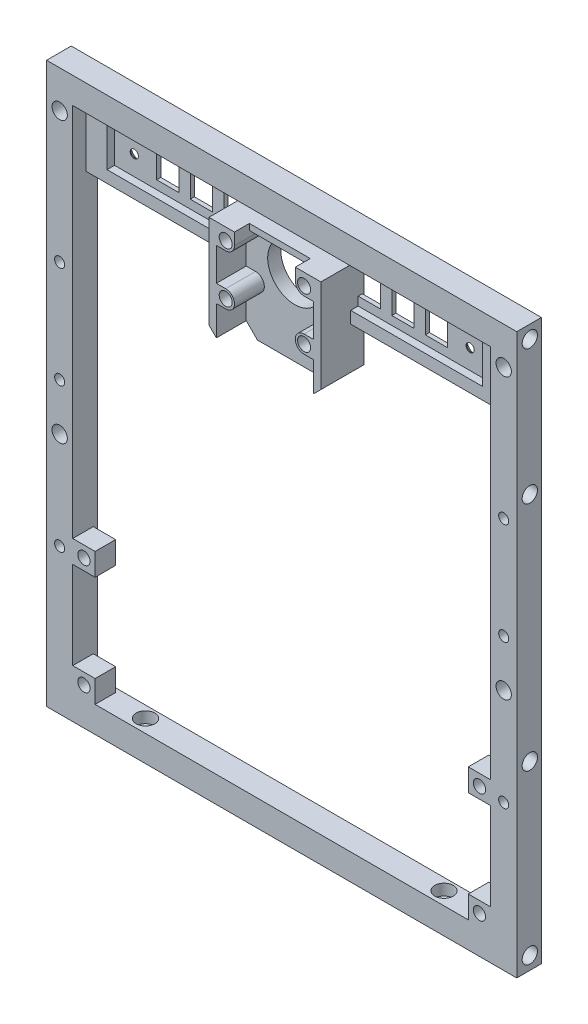
SolidWorks part; units mm, degrees
ref_plane "Front Plane" through (0, 0, 0) normal (0, 0, 1) x (1, 0, 0)
ref_plane "Top Plane" through (0, 0, 0) normal (0, 1, 0) x (1, 0, 0)
ref_plane "Right Plane" through (0, 0, 0) normal (1, 0, 0) x (0, 0, -1)
sketch "Sketch1" plane through (0, 0, 0) normal (0, 0, 1) x (1, 0, 0)
  line L1 (-63, -75) -> (63, -75)
  line L2 (-63, -75) -> (-63, 75)
  line L3 (-63, 75) -> (63, 75)
  line L4 (63, -75) -> (63, 75)
  line L5 (-63, -75) -> (63, 75) construction
  line L6 (-63, 75) -> (63, -75) construction
  line L7 (-56, -68) -> (56, -68)
  line L8 (-56, -68) -> (-56, 68)
  line L9 (-56, 68) -> (56, 68)
  line L10 (56, -68) -> (56, 68)
  line L11 (-56, -68) -> (56, 68) construction
  line L12 (-56, 68) -> (56, -68) construction
  point P0 (0, 0)
  point P6 (0, 0)
  dimension "D1" = 126
  dimension "D2" = 150
  dimension "D3" = 7
  dimension "D4" = 7
extrude "Boss-Extrude1" add sketch "Sketch1" along normal blind 7
sketch "Sketch2" plane through (-63, 0, 0) normal (-1, 0, 0) x (0, 0, 1)
  line L0 (3.5, 71.5) -> (3.5, -71.5) construction
  line L1 (7, 75) -> (0, 75) construction
  circle A0 centre (3.5, -71.5) radius 2.05
  circle A2 centre (3.5, 71.5) radius 2.05
  circle A3 centre (3.5, 35.5) radius 2.05
  circle A4 centre (3.5, -26.5) radius 2.05
  point P2 (3.5, 0)
  point P7 (3.5, 75)
  dimension "D2" = 4.1
  dimension "D3" = 36
  dimension "D4" = 45
  dimension "D1" = 3.5
extrude "Cut-Extrude1" cut sketch "Sketch2" against normal blind 6
mirror "Mirror1" about plane through (0, 0, 0) normal (1, 0, 0) of "Cut-Extrude1"
sketch "Sketch3" plane through (0, -68, 0) normal (0, 1, 0) x (1, 0, 0)
  line L0 (0, 0) -> (0, -7) construction
  line L1 (-56, 0) -> (56, 0) construction
  line L2 (-56, -7) -> (56, -7) construction
  line L3 (40, -3.5) -> (-40, -3.5) construction
  circle A0 centre (40, -3.5) radius 1.35
  circle A1 centre (-40, -3.5) radius 1.35
  point P9 (0, -3.5)
  dimension "D1" = 2.7
  dimension "D2" = 80
extrude "Cut-Extrude2" cut sketch "Sketch3" against normal through all
sketch "Sketch4" plane through (0, -68, 0) normal (0, 1, 0) x (1, 0, 0)
  circle A0 centre (40, -3.5) radius 2.5
  circle A1 centre (-40, -3.5) radius 2.5
  dimension "D1" = 5
extrude "Cut-Extrude3" cut sketch "Sketch4" against normal blind 3
sketch "Sketch5" plane through (0, 0, 0) normal (0, 0, -1) x (-1, 0, 0)
  line L0 (-59.5, -75) -> (-59.5, 75) construction
  line L1 (63, -75) -> (-63, -75) construction
  line L2 (-63, 75) -> (63, 75) construction
  line L3 (-56, 0) -> (-63, 0) construction
  line L4 (-56, -68) -> (-56, 68) construction
  line L5 (-63, -75) -> (-63, 75) construction
  line L6 (0, 75) -> (0, -75) construction
  line L7 (56, -68) -> (-56, -68) construction
  circle A0 centre (-59.5, 2.6) radius 1.35
  circle A1 centre (59.5, 2.6) radius 1.35
  circle A2 centre (-59.5, -36) radius 1.35
  circle A3 centre (59.5, -36) radius 1.35
  circle A4 centre (-59.5, 29.9) radius 1.35
  circle A5 centre (59.5, 29.9) radius 1.35
  point P12 (-59.5, 0)
  point P13 (-59.5, 0)
  dimension "D1" = 2.7
  dimension "D2" = 2.6
  dimension "D3" = 32
  dimension "D4" = 45.1
extrude "Cut-Extrude4" cut sketch "Sketch5" against normal through all
sketch "Sketch6" plane through (0, 0, 0) normal (0, 0, -1) x (-1, 0, 0)
  circle A0 centre (-59.5, 2.6) radius 2.5
  circle A1 centre (59.5, 2.6) radius 2.5
  circle A2 centre (-59.5, -36) radius 2.5
  circle A3 centre (59.5, -36) radius 2.5
  circle A4 centre (-59.5, 29.9) radius 2.5
  circle A5 centre (59.5, 29.9) radius 2.5
  dimension "D1" = 5
extrude "Cut-Extrude5" cut sketch "Sketch6" against normal blind 3
sketch "Sketch7" plane through (0, 0, 0) normal (0, 0, -1) x (-1, 0, 0)
  line L0 (-56, 68) -> (-63, 68) construction
  line L1 (-63, -75) -> (-63, 75) construction
  line L2 (-59.5, 65) -> (-59.5, -10) construction
  line L3 (-63, 75) -> (63, 75) construction
  circle A0 centre (-59.5, 65) radius 2.05
  circle A1 centre (-59.5, -10) radius 2.05
  point P8 (-59.5, 68)
  dimension "D1" = 4.1
  dimension "D2" = 10
  dimension "D3" = 75
extrude "Cut-Extrude6" cut sketch "Sketch7" against normal through all
mirror "Mirror2" about plane through (0, 0, 0) normal (1, 0, 0) of "Cut-Extrude6"
sketch "Sketch8" plane through (0, 0, 3) normal (0, 0, -1) x (-1, 0, 0)
  line L0 (-60.85, 32.0042) -> (-60.85, 27.7958)
  line L2 (-60.85, 0.4958) -> (-60.85, 4.7042)
  line L4 (-58.15, 0.4958) -> (-58.15, 4.7042)
  line L5 (-60.85, 0.4958) -> (-58.15, 4.7042) construction
  line L6 (-60.85, 4.7042) -> (-58.15, 0.4958) construction
  line L8 (-60.85, -38.1042) -> (-60.85, -33.8958)
  line L10 (-58.15, -38.1042) -> (-58.15, -33.8958)
  line L11 (-60.85, -38.1042) -> (-58.15, -33.8958) construction
  line L12 (-60.85, -33.8958) -> (-58.15, -38.1042) construction
  line L13 (-58.15, 32.0042) -> (-58.15, 27.7958)
  circle A0 centre (-59.5, 2.6) radius 2.5 construction
  circle A1 centre (-59.5, -36) radius 2.5 construction
  circle A2 centre (-59.5, -36) radius 2.5 construction
  arc A3 (-58.15, 4.7042) -> (-60.85, 4.7042) centre (-59.5, 2.6) ccw
  arc A4 (-58.15, -33.8958) -> (-60.85, -33.8958) centre (-59.5, -36) ccw
  circle A5 centre (-59.5, 2.6) radius 1.35 construction
  circle A6 centre (-59.5, -36) radius 1.35 construction
  arc A7 (-60.85, -38.1042) -> (-58.15, -38.1042) centre (-59.5, -36) ccw
  arc A8 (-60.85, 0.4958) -> (-58.15, 0.4958) centre (-59.5, 2.6) ccw
  circle A9 centre (-59.5, 29.9) radius 2.5 construction
  arc A10 (-60.85, 32.0042) -> (-58.15, 32.0042) centre (-59.5, 29.9) cw
  arc A11 (-58.15, 27.7958) -> (-60.85, 27.7958) centre (-59.5, 29.9) cw
  point P0 (-59.5, 2.6)
  point P8 (-59.5, -36)
extrude "Cut-Extrude7" cut sketch "Sketch8" against normal blind 0.2
sketch "Sketch9" plane through (0, 0, 3.2) normal (0, 0, -1) x (-1, 0, 0)
  line L0 (-58.15, 2.6) -> (-58.15, 4.7042) construction
  line L1 (-60.85, 1.25) -> (-58.15, 1.25)
  line L2 (-60.85, 1.25) -> (-60.85, 3.95)
  line L3 (-60.85, 3.95) -> (-58.15, 3.95)
  line L4 (-58.15, 1.25) -> (-58.15, 3.95)
  line L5 (-60.85, 1.25) -> (-58.15, 3.95) construction
  line L6 (-60.85, 3.95) -> (-58.15, 1.25) construction
  line L7 (-58.15, -38.1042) -> (-58.15, -33.8958) construction
  line L8 (-60.85, -37.35) -> (-58.15, -37.35)
  line L9 (-60.85, -37.35) -> (-60.85, -34.65)
  line L10 (-60.85, -34.65) -> (-58.15, -34.65)
  line L11 (-58.15, -37.35) -> (-58.15, -34.65)
  line L12 (-60.85, -37.35) -> (-58.15, -34.65) construction
  line L13 (-60.85, -34.65) -> (-58.15, -37.35) construction
  arc A0 (-58.15, 2.6) -> (-60.85, 2.6) centre (-59.5, 2.6) ccw construction
  point P0 (-59.5, 2.6)
  point P8 (-59.5, -36)
extrude "Cut-Extrude8" cut sketch "Sketch9" against normal blind 0.2
mirror "Mirror3" about plane through (0, 0, 0) normal (1, 0, 0) of "Cut-Extrude8", "Cut-Extrude7"
sketch "Sketch10" plane through (0, 0, 7) normal (0, 0, 1) x (1, 0, 0)
  line L0 (56, -68) -> (56, 68) construction
  line L1 (56, -68) -> (50, -68)
  line L2 (56, -68) -> (56, -62)
  line L3 (56, -62) -> (50, -62)
  line L4 (50, -68) -> (50, -62)
  line L5 (56, -38.5) -> (50, -38.5)
  line L6 (56, -38.5) -> (56, -32.5)
  line L7 (56, -32.5) -> (50, -32.5)
  line L8 (50, -38.5) -> (50, -32.5)
  line L9 (-56, -68) -> (56, -68) construction
  dimension "D1" = 6
  dimension "D2" = 35.5
extrude "Boss-Extrude2" add sketch "Sketch10" against normal offset from surface (5.5 mm away) 1.5 up to face at (-57.45, -10, 0)
sketch "Sketch11" plane through (0, 0, 1.5) normal (0, 0, -1) x (-1, 0, 0)
  line L0 (-56, -38.5) -> (-50, -32.5) construction
  line L2 (-56, -68) -> (-50, -62) construction
  circle A0 centre (-53, -35.5) radius 1.65
  circle A1 centre (-53, -65) radius 1.65
  dimension "D1" = 3.3
extrude "Cut-Extrude9" cut sketch "Sketch11" against normal through all
mirror "Mirror4" about plane through (0, 0, 0) normal (1, 0, 0) of "Cut-Extrude9", "Boss-Extrude2"
sketch "Sketch12" plane through (0, 0, 0) normal (0, 0, -1) x (-1, 0, 0)
  line L0 (56, 68) -> (56, -68) construction
  line L1 (-56, 68) -> (56, 68)
  line L2 (-56, 68) -> (-56, 51)
  line L3 (-56, 51) -> (56, 51)
  line L4 (56, 68) -> (56, 51)
  dimension "D1" = 17
extrude "Boss-Extrude3" add sketch "Sketch12" against normal blind 1.5
sketch "Sketch13" plane through (0, 0, 1.5) normal (0, 0, 1) x (1, 0, 0)
  line L0 (-56, 68) -> (56, 51) construction
  line L2 (-50.3, 54.2) -> (50.3, 54.2)
  line L3 (-50.3, 54.2) -> (-50.3, 64.8)
  line L4 (-50.3, 64.8) -> (50.3, 64.8)
  line L5 (50.3, 54.2) -> (50.3, 64.8)
  line L6 (-50.3, 54.2) -> (50.3, 64.8) construction
  line L7 (-50.3, 64.8) -> (50.3, 54.2) construction
  line L8 (-56, 51) -> (56, 51)
  line L9 (-56, 51) -> (-56, 68)
  line L10 (-56, 68) -> (56, 68)
  line L11 (56, 51) -> (56, 68)
  line L12 (-56, 51) -> (56, 68) construction
  line L13 (-56, 68) -> (56, 51) construction
  point P4 (0, 59.5)
  point P9 (0, 59.5)
  dimension "D1" = 100.6
  dimension "D2" = 10.6
extrude "Boss-Extrude4" add sketch "Sketch13" along normal blind 2
sketch "Sketch14" plane through (0, 0, 1.5) normal (0, 0, 1) x (1, 0, 0)
  line L0 (0, 64.8) -> (0, 54.2) construction
  line L1 (50.3, 64.8) -> (-50.3, 64.8) construction
  line L2 (-50.3, 54.2) -> (50.3, 54.2) construction
  line L3 (-50.3, 59.5) -> (50.3, 59.5) construction
  line L4 (50.3, 54.2) -> (50.3, 64.8) construction
  line L5 (-33, 62.5) -> (-39, 62.5)
  line L6 (-3.25, 57.5) -> (3.25, 57.5)
  line L7 (-3.25, 57.5) -> (-3.25, 61.5)
  line L8 (-3.25, 61.5) -> (3.25, 61.5)
  line L9 (3.25, 57.5) -> (3.25, 61.5)
  line L10 (-3.25, 57.5) -> (3.25, 61.5) construction
  line L11 (-3.25, 61.5) -> (3.25, 57.5) construction
  line L12 (6, 56.5) -> (12, 56.5)
  line L13 (6, 56.5) -> (6, 62.5)
  line L14 (6, 62.5) -> (12, 62.5)
  line L15 (12, 56.5) -> (12, 62.5)
  line L16 (6, 56.5) -> (12, 62.5) construction
  line L17 (6, 62.5) -> (12, 56.5) construction
  line L18 (15, 56.5) -> (21, 56.5)
  line L19 (15, 56.5) -> (15, 62.5)
  line L20 (15, 62.5) -> (21, 62.5)
  line L21 (21, 56.5) -> (21, 62.5)
  line L22 (15, 56.5) -> (21, 62.5) construction
  line L23 (15, 62.5) -> (21, 56.5) construction
  line L24 (24, 56.5) -> (30, 56.5)
  line L25 (24, 56.5) -> (24, 62.5)
  line L26 (24, 62.5) -> (30, 62.5)
  line L27 (30, 56.5) -> (30, 62.5)
  line L28 (24, 56.5) -> (30, 62.5) construction
  line L29 (24, 62.5) -> (30, 56.5) construction
  line L30 (33, 56.5) -> (39, 56.5)
  line L31 (33, 56.5) -> (33, 62.5)
  line L32 (33, 62.5) -> (39, 62.5)
  line L33 (39, 56.5) -> (39, 62.5)
  line L34 (33, 56.5) -> (39, 62.5) construction
  line L35 (33, 62.5) -> (39, 56.5) construction
  line L36 (-39, 56.5) -> (-39, 62.5)
  line L37 (-33, 56.5) -> (-39, 56.5)
  line L38 (-33, 56.5) -> (-33, 62.5)
  line L39 (-24, 62.5) -> (-30, 62.5)
  line L40 (-30, 56.5) -> (-30, 62.5)
  line L41 (-24, 56.5) -> (-30, 56.5)
  line L42 (-24, 56.5) -> (-24, 62.5)
  line L43 (-15, 62.5) -> (-21, 62.5)
  line L44 (-21, 56.5) -> (-21, 62.5)
  line L45 (-15, 56.5) -> (-21, 56.5)
  line L46 (-15, 56.5) -> (-15, 62.5)
  line L47 (-6, 62.5) -> (-12, 62.5)
  line L48 (-12, 56.5) -> (-12, 62.5)
  line L49 (-6, 56.5) -> (-12, 56.5)
  line L50 (-6, 56.5) -> (-6, 62.5)
  circle A0 centre (-45, 59.5) radius 1.3 construction
  circle A1 centre (45, 59.5) radius 1.3 construction
  point P6 (0, 59.5)
  point P11 (0, 59.5)
  point P16 (9, 59.5)
  point P21 (18, 59.5)
  point P26 (27, 59.5)
  point P31 (36, 59.5)
  dimension "D10" = 2.6
  dimension "D9" = 45
  dimension "D1" = 6.5
  dimension "D2" = 4
  dimension "D3" = 6
  dimension "D4" = 9
  dimension "D5" = 9
  dimension "D6" = 9
  dimension "D7" = 9
  dimension "D8" = 45
extrude "Cut-Extrude10" cut sketch "Sketch14" against normal through all
sketch "Sketch15" plane through (0, 0, 1.5) normal (0, 0, 1) x (1, 0, 0)
  circle A0 centre (-45, 59.5) radius 1
  circle A1 centre (45, 59.5) radius 1
  dimension "D1" = 2
extrude "Boss-Extrude5" add sketch "Sketch15" along normal up to surface (2 mm away) up to face at (0, 59.5, 3.5)
chamfer "Chamfer1" distance 0.4 angle 45 4 edges at (-56, -8.5, 0) (56, -8.5, 0) (0, -68, 0) (0, 51, 0)
chamfer "Chamfer2" distance 0.4 angle 45 4 edges at (0, 75, 0) (-63, 0, 0) (0, -75, 0) (63, 0, 0)
chamfer "Chamfer3" distance 0.4 angle 45 36 edges at (-36, 56.5, 0) (-39, 59.5, 0) (-36, 62.5, 0) (-33, 59.5, 0) (-27, 56.5, 0) (-30, 59.5, 0) (-27, 62.5, 0) (-24, 59.5, 0) (-18, 56.5, 0) (-21, 59.5, 0) (-18, 62.5, 0) (-15, 59.5, 0) (-9, 56.5, 0) (-12, 59.5, 0) (-9, 62.5, 0) (-6, 59.5, 0) (0, 57.5, 0) (-3.25, 59.5, 0) (0, 61.5, 0) (3.25, 59.5, 0) (9, 56.5, 0) (6, 59.5, 0) (9, 62.5, 0) (12, 59.5, 0) (18, 56.5, 0) (15, 59.5, 0) (18, 62.5, 0) (21, 59.5, 0) (36, 56.5, 0) (33, 59.5, 0) (36, 62.5, 0) (39, 59.5, 0) (27, 56.5, 0) (24, 59.5, 0) (27, 62.5, 0) (30, 59.5, 0)
sketch "Sketch16" plane through (0, 0, 7) normal (0, 0, 1) x (1, 0, 0)
  line L0 (-50, 51) -> (-50, 54.2)
  line L1 (-56, -32.5) -> (-50, -32.5)
  line L2 (-56, -32.5) -> (-56, -26.5)
  line L3 (-56, -26.5) -> (-50, -26.5)
  line L4 (-50, -32.5) -> (-50, -26.5)
  line L5 (56, -32.5) -> (50, -32.5)
  line L6 (56, -32.5) -> (56, -26.5)
  line L7 (56, -26.5) -> (50, -26.5)
  line L8 (50, -32.5) -> (50, -26.5)
  line L9 (56, 51) -> (50, 51) construction
  line L10 (56, 51) -> (56, 45)
  line L11 (56, 45) -> (50, 45)
  line L12 (50, 51) -> (50, 45)
  line L13 (-56, 51) -> (-50, 51) construction
  line L14 (-56, 51) -> (-56, 45)
  line L15 (-56, 45) -> (-50, 45)
  line L16 (-50, 51) -> (-50, 45)
  line L17 (-50.3, 54.2) -> (50.3, 54.2) construction
  line L18 (-50, 54.2) -> (-56, 54.2)
  line L19 (-56, 68) -> (-56, 51) construction
  line L20 (-56, 54.2) -> (-56, 51)
  line L21 (50, 51) -> (50, 54.2)
  line L22 (50, 54.2) -> (56, 54.2)
  line L23 (56, 51) -> (56, 68) construction
  line L24 (56, 54.2) -> (56, 51)
  dimension "D1" = 6
extrude "Boss-Extrude7" add sketch "Sketch16" against normal offset from surface (5.5 mm away) 1.5 up to face at (-36, 59.5, 0)
sketch "Sketch17" plane through (0, 0, 1.5) normal (0, 0, -1) x (-1, 0, 0)
  line L0 (-50, 45) -> (50, -26.5) construction
  line L1 (-50, -26.5) -> (-50, -38.5) construction
  line L2 (-53, -29.5) -> (53, -29.5) construction
  line L3 (-53, -29.5) -> (-53, 48) construction
  line L4 (-53, 48) -> (53, 48) construction
  line L5 (53, -29.5) -> (53, 48) construction
  line L6 (-53, -29.5) -> (53, 48) construction
  line L7 (-53, 48) -> (53, -29.5) construction
  line L8 (50, -26.5) -> (56, -26.5) construction
  circle A0 centre (-53, -29.5) radius 1.65
  circle A1 centre (53, -29.5) radius 1.65
  circle A2 centre (53, 48) radius 1.65
  circle A3 centre (-53, 48) radius 1.65
  point P4 (0, 9.25)
  dimension "D3" = 3.3
  dimension "D1" = 3
  dimension "D2" = 3
extrude "Cut-Extrude11" cut sketch "Sketch17" against normal through all
sketch "Sketch18" plane through (0, 0, 1.5) normal (0, 0, 1) x (1, 0, 0)
  circle A0 centre (-45, 59.5) radius 1.1
  circle A1 centre (45, 59.5) radius 1.1
  dimension "D1" = 2.2
extrude "Cut-Extrude12" cut sketch "Sketch18" against normal through all both and the other way through all
chamfer "Chamfer4" distance 1.3 angle 45 2 edges at (-43.9, 59.5, 0) (46.1, 59.5, 0)
sketch "Skizze1" plane through (0, 0, 7) normal (0, 0, 1) x (1, 0, 0)
  line L0 (-56, -38.5) -> (-56, -26.5) construction
  line L1 (56, 51) -> (-56, 51)
  line L2 (56, 51) -> (56, -32.5)
  line L3 (56, -32.5) -> (-56, -32.5)
  line L4 (-56, 51) -> (-56, -32.5)
extrude "Schnitt-Linear austragen1" cut sketch "Skizze1" against normal up to surface (5.5 mm away) up to face at (-54.65, 48, 1.5)
sketch "Skizze2" plane through (0, 0, 7) normal (0, 0, 1) x (1, 0, 0)
  line L1 (-56, 54.2) -> (56, 54.2)
  line L2 (-56, 54.2) -> (-56, 51)
  line L3 (-56, 51) -> (56, 51)
  line L4 (56, 54.2) -> (56, 51)
extrude "Schnitt-Linear austragen2" cut sketch "Skizze2" against normal up to surface (3.5 mm away) up to face at (0, 52.6, 3.5)
sketch "Skizze3" plane through (0, 0, 3.5) normal (0, 0, 1) x (1, 0, 0)
  line L0 (0, 51) -> (0, 14.1518) construction
  line L2 (50.3, 64.8) -> (-50.3, 64.8) construction
  line L3 (-15, 34.8) -> (15, 34.8)
  line L4 (-15, 34.8) -> (-15, 64.8)
  line L5 (-15, 64.8) -> (15, 64.8)
  line L6 (15, 34.8) -> (15, 64.8)
  line L7 (-15, 34.8) -> (15, 64.8) construction
  line L8 (-15, 64.8) -> (15, 34.8) construction
  line L10 (-12.5, 37.3) -> (12.5, 37.3)
  line L11 (-12.5, 37.3) -> (-12.5, 62.3)
  line L12 (-12.5, 62.3) -> (12.5, 62.3)
  line L13 (12.5, 37.3) -> (12.5, 62.3)
  line L14 (-12.5, 37.3) -> (12.5, 62.3) construction
  line L15 (-12.5, 62.3) -> (12.5, 37.3) construction
  point P1 (0, 49.8)
  point P9 (0, 49.8)
  point P16 (0, 45.1863)
  point P17 (-12.5, 37.3)
  line M7 (-56, 51) -> (56, 51)
  line M10 (50.3, 54.2) -> (-50.3, 54.2)
  line M12 (-50.3, 64.8) -> (50.3, 64.8)
  dimension "D1" = 30
  dimension "D2" = 25
extrude "Aufsatz-Linear austragen1" add sketch "Skizze3" against normal up to surface (3.5 mm away) contours L10 L13 L11 M7 | L13 L10 L11 L4 L3 L6 M7 | L13 L12 L11 M10 | L13 L6 L4 L11 L12 M10 M12 | L13 L6 M7 M10 | L13 L11 M7 M10 | L11 L4 M7 M10 region at (-14.6591, 42.9, 3.5) region at (-13.75, 52.6, 3.5) region at (13.75, 52.6, 3.5) region at (-14.6818, 59.5, 3.5) region at (0, 44.15, 3.5) region at (0, 52.6, 3.5) region at (0, 58.25, 3.5) up to face at (-47.4, 59.5, 0)
sketch "Skizze4" plane through (0, 0, 3.5) normal (0, 0, 1) x (1, 0, 0)
  line L1 (15, 54.2) -> (15, 64.8) construction
  line L3 (15, 54.2) -> (15, 64.8)
  line L4 (0, 34.8) -> (0, 64.8) construction
  line L5 (-15, 34.8) -> (15, 34.8) construction
  line L6 (-15, 34.8) -> (-15, 64.8) construction
  line L7 (-15, 64.8) -> (15, 64.8) construction
  line L8 (15, 34.8) -> (15, 64.8) construction
  line L13 (13, 59.2753) -> (13, 50.4753)
  line L14 (-13, 59.2753) -> (-13, 50.4753)
  line L15 (-7.25, 141.3696) -> (7.25, 141.3696)
  line L16 (-7.25, 141.3696) -> (-7.25, 155.8696)
  line L17 (-7.25, 155.8696) -> (7.25, 155.8696)
  line L18 (7.25, 141.3696) -> (7.25, 155.8696)
  line L19 (-7.25, 141.3696) -> (7.25, 155.8696) construction
  line L20 (-7.25, 155.8696) -> (7.25, 141.3696) construction
  line L21 (15, 34.8) -> (15, 64.8)
  line L22 (15, 64.8) -> (-15, 64.8)
  line L23 (-15, 64.8) -> (-15, 34.8)
  line L25 (8.15, 63.1639) -> (-8.15, 63.1639)
  line L33 (14.1556, 39.6253) -> (-12.2672, 39.6253) construction
  line L35 (11.045, 38.1615) -> (11.045, 38.755)
  line L37 (13, 34.8) -> (15, 34.8)
  line L39 (-8.15, 61.6253) -> (-8.15, 63.1639)
  line L40 (-10.5, 59.2753) -> (-13, 59.2753)
  line L41 (8.15, 61.6253) -> (8.15, 63.1639)
  line L42 (10.5, 59.2753) -> (13, 59.2753)
  line L45 (13, 34.8) -> (13, 45.7753)
  line L47 (-10.5, 50.4753) -> (-13, 50.4753)
  line L48 (-10.5, 45.7753) -> (-13, 45.7753)
  line L50 (10.5, 45.7753) -> (13, 45.7753)
  line L51 (10.5, 50.4753) -> (13, 50.4753)
  line L53 (-15, 34.8) -> (-13, 34.8)
  line L55 (-13, 45.7753) -> (-13, 34.8)
  line L58 (-7.25, 48.0253) -> (7.25, 48.0253) construction
  line L63 (-7.25, 48.0253) -> (-7.25, 62.5253) construction
  line L64 (-7.25, 62.5253) -> (7.25, 62.5253) construction
  line L65 (7.25, 48.0253) -> (7.25, 62.5253)
  line L66 (-7.25, 48.0253) -> (7.25, 62.5253) construction
  line L67 (-7.25, 62.5253) -> (7.25, 48.0253) construction
  circle A2 centre (-10.5, 61.6253) radius 1.75
  circle A3 centre (10.5, 61.6253) radius 1.75
  arc A7 (8.15, 61.6253) -> (10.5, 59.2753) centre (10.5, 61.6253) ccw
  arc A10 (-10.5, 59.2753) -> (-8.15, 61.6253) centre (-10.5, 61.6253) ccw
  circle A11 centre (0, 55.2753) radius 7.25
  circle A12 centre (-10.5, 48.1253) radius 1.75
  circle A14 centre (10.5, 48.1253) radius 1.75
  arc A15 (-10.5, 45.7753) -> (-10.5, 50.4753) centre (-10.5, 48.1253) ccw
  arc A16 (10.5, 50.4753) -> (10.5, 45.7753) centre (10.5, 48.1253) ccw
  point P4 (0, 48.7936)
  point P7 (0, 55.2753)
  point P10 (0, 148.6196)
  point P11 (0, 148.6196)
  point P37 (0, 148.6196)
  point P40 (0, 55.2753)
  point P71 (0, 64.8)
  dimension "D4" = 13.5
  dimension "D5" = 3.5
  dimension "D6" = 0.6
  dimension "D7" = 2
  dimension "D8" = 22
  dimension "D2" = 14.5
  dimension "D3" = 21
  dimension "D9" = 9.1682
  dimension "D10" = 15.65
  dimension "D11" = 14.5
extrude "Schnitt-Linear austragen3" cut sketch "Skizze4" against normal blind 10 contours L15 L18 L17 L16 | L63 L58 L65 L64 | A11 region at (0, 148.6196, 3.5)
extrude "Aufsatz-Linear austragen2" add sketch "Skizze4<3>" along normal blind 8 contours A2 | A7 A3 region at (14.5757, 44.5, 3.5)
sketch "Skizze4<3>" plane through (0, 0, 3.5) normal (0, 0, 1) x (1, 0, 0) same geometry as "Skizze4"
extrude "Schnitt-Linear austragen4" cut sketch "Skizze4<4>" against normal blind 8 contours A3 | A2
sketch "Skizze4<4>" plane through (0, 0, 3.5) normal (0, 0, 1) x (1, 0, 0) same geometry as "Skizze4"
sketch "Skizze6" plane through (0, 0, 11.5) normal (0, 0, 1) x (1, 0, 0)
  line L0 (15, 64.8) -> (-15, 64.8) construction
  line L1 (-8.15, 63.1639) -> (8.15, 63.1639)
  line L2 (-8.15, 63.1639) -> (-8.15, 64.8)
  line L3 (-8.15, 64.8) -> (8.15, 64.8)
  line L4 (8.15, 63.1639) -> (8.15, 64.8)
extrude "Schnitt-Linear austragen5" cut sketch "Skizze6" against normal blind 4
chamfer "Fase1" distance 5 angle 45 2 edges at (-15, 34.8, 5.75) (15, 34.8, 5.75)
